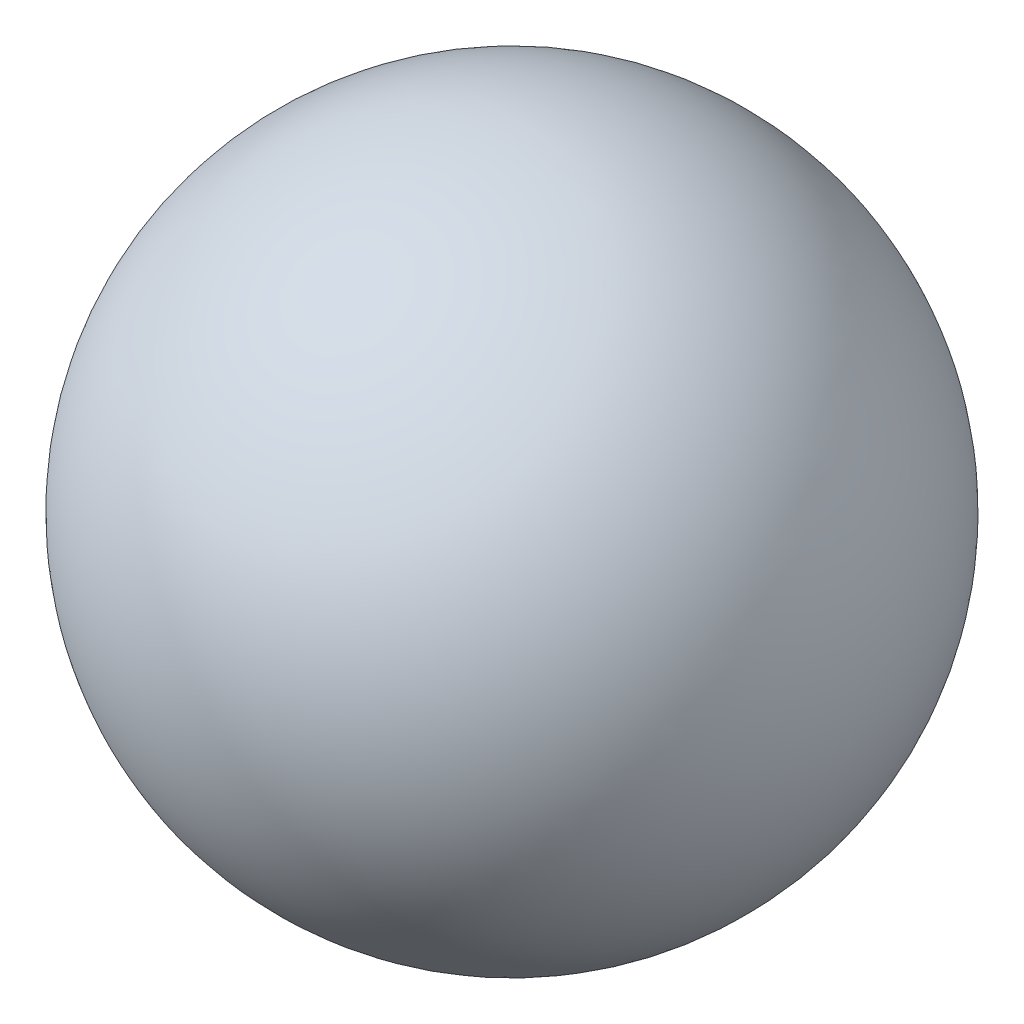
SolidWorks part; units mm, degrees
material "Polybutadiene (PB)"
ref_plane "Front Plane" through (0, 0, 0) normal (0, 0, 1) x (1, 0, 0)
ref_plane "Top Plane" through (0, 0, 0) normal (0, 1, 0) x (1, 0, 0)
ref_plane "Right Plane" through (0, 0, 0) normal (1, 0, 0) x (0, 0, -1)
other "Configuration Table"
sketch "Sketch1" plane through (0, 0, 0) normal (0, 1, 0) x (1, 0, 0)
  line L0 (0, 0) -> (0, 21.35) construction
  line L1 (0, 0) -> (0, -21.35) construction
  line L2 (0, 21.35) -> (0, -21.35)
  arc A0 (0, 21.35) -> (0, -21.35) centre (0, 0) ccw
  point P3 (0.3497, -21.35)
  dimension "D1" = 42.7
revolve "Revolve3" add sketch "Sketch1" angle 360 about L2
